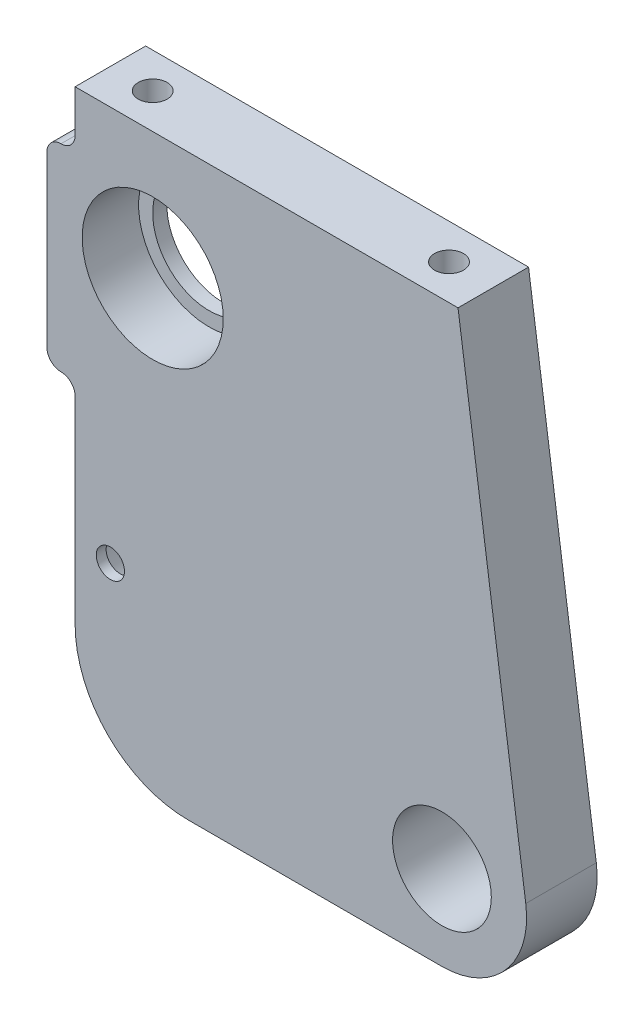
SolidWorks part; units mm, degrees
material "7075-T6, Plate (SS)"
ref_plane "前视基准面" through (0, 0, 0) normal (0, 0, 1) x (1, 0, 0)
ref_plane "上视基准面" through (0, 0, 0) normal (0, 1, 0) x (1, 0, 0)
ref_plane "右视基准面" through (0, 0, 0) normal (1, 0, 0) x (0, 0, -1)
sketch "草图1" plane through (0, 0, 0) normal (0, 0, 1) x (1, 0, 0)
  line L1 (0, 0) -> (34, 0)
  line L2 (0, 0) -> (0, -41)
  line L3 (0, -41) -> (34, -41)
  line L4 (34, 0) -> (34, -41)
  dimension "D1" = 34
  dimension "D3" = 41
extrude "拉伸1" add sketch "草图1" along normal blind 5
fillet "圆角1" radius 8 1 edges at (0, -41, 2.5)
sketch "草图2" plane through (0, 0, 5) normal (0, 0, 1) x (1, 0, 0)
  line L0 (0, 0) -> (0, -33) construction
  line L2 (8, -41) -> (34, -41) construction
  circle A0 centre (26, -35) radius 3.5
  dimension "D2" = 6
  dimension "D3" = 7
  dimension "D1" = 26
extrude "拉伸2" cut sketch "草图2" against normal up to surface (5 mm away) up to face at (14.8686, -23.3314, 0)
sketch "草图3" plane through (0, 0, 5) normal (0, 0, 1) x (1, 0, 0)
  line L0 (0, 0) -> (0, -33) construction
  line L1 (0, -41) -> (34, -41) construction
  circle A0 centre (5.5, -9) radius 4
  dimension "D1" = 5.5
  dimension "D2" = 32
  dimension "D3" = 8
extrude "拉伸3" cut sketch "草图3" against normal up to surface (5 mm away) up to face at (29.5, -35, 0)
sketch "草图4" plane through (0, 0, 5) normal (0, 0, 1) x (1, 0, 0)
  circle A0 centre (5.5, -9) radius 5
  dimension "D1" = 10
extrude "拉伸4" cut sketch "草图4" against normal blind 4
sketch "草图5" plane through (0, 0, 0) normal (0, 1, 0) x (1, 0, 0)
  line L0 (3, -2.5) -> (24, -2.5)
  line L1 (34, 0) -> (0, 0) construction
  line L2 (17, 0) -> (17, -2.5) construction
  line L3 (0, -5) -> (0, 0) construction
  dimension "D1" = 2.5
  dimension "D2" = 21
  dimension "D3" = 3
hole_wizard "M2.5 螺纹孔1" positions "3D草图1" profile "草图6" tap size "M2.5" standard "GB"
sketch3d "3D草图1"
  point P0 (3, 0, 2.5)
  point P3 (24, 0, 2.5)
sketch "草图6" plane through (3, 0, 2.5) normal (1, 0, 0) x (0, 0, 1)
  line L0 (0, 0) -> (0, 7.9659)
  line L1 (0, 7.9659) -> (1.025, 7.35)
  line L2 (1.025, 7.35) -> (1.025, 0)
  line L5 (1.025, 0) -> (0, 0)
  line L10 (0, 7.9659) -> (-1.025, 7.35) construction
  line L11 (0, -6.35) -> (0, 107.95) construction
  dimension "螺纹孔钻头直径" = 2.05
  dimension "螺纹孔钻头深度" = 7.35
  dimension "导头角度" = 118
cosmetic thread "孔螺蚊线1" parameters "D1"=6, "D2"=2.5
cosmetic thread "孔螺蚊线2" parameters "D1"=6, "D2"=2.5
chamfer "倒角1" [suppressed] distance 0.5 angle 45
chamfer "倒角2" [suppressed] distance 0.5 angle 45
sketch "草图7" plane through (0, 0, 0) normal (0, 0, -1) x (-1, 0, 0)
  line L1 (-8, -41) -> (-34, -41) construction
  line L2 (-31.9416, -34.165) -> (-27.14, 0)
  line L3 (-34, 0) -> (0, 0) construction
  line L4 (-26, -41) -> (-34, -41)
  line L5 (-34, -41) -> (-34, 0) construction
  line L6 (-34, -41) -> (-34, 0)
  line L7 (-34, 0) -> (-27.14, 0)
  arc A0 (-31.9416, -34.165) -> (-26, -41) centre (-26, -35) ccw
  circle A1 centre (-26, -35) radius 3.5 construction
  dimension "D1" = 6
  dimension "D2" = 8
extrude "拉伸5" cut sketch "草图7" against normal up to surface (5 mm away) up to face at (10.5, -9, 5)
sketch "Sketch1" plane through (0, 0, 0) normal (0, 0, -1) x (-1, 0, 0)
  line L0 (-26, -41) -> (-12, -41)
  line L1 (0, 0) -> (0, -33) construction
  line L2 (0, -28.0198) -> (0, -29)
  line L3 (-29.4415, -39.9149) -> (0, -28.0198)
  line L4 (-26, -35) -> (-29.4415, -39.9149) construction
  line L5 (-8, -41) -> (-26, -41) construction
  arc A0 (-31.9416, -34.165) -> (-26, -41) centre (-26, -35) ccw construction
  arc A1 (-29.4415, -39.9149) -> (-26, -41) centre (-26, -35) ccw
  arc A3 (0, -29) -> (-12, -41) centre (-12, -29) cw
  dimension "D1" = 12
  dimension "D2" = 55
  dimension "D3" = 22
  dimension "D4" = 0
sketch "草图8" plane through (0, 0, 0) normal (0, 0, -1) x (-1, 0, 0)
  line L0 (-8, -41) -> (-26, -41) construction
  line L1 (0, 0) -> (0, -33) construction
  circle A0 centre (-2.5, -28) radius 1
  dimension "D3" = 2
  dimension "D1" = 13
  dimension "D2" = 2.5
extrude "拉伸6" cut sketch "草图8" against normal up to surface (5 mm away) up to face at (15.497, -25.3626, 5)
sketch "草图9" plane through (0, 0, 0) normal (0, 0, -1) x (-1, 0, 0)
  line L3 (-7.1, -31.0997) -> (-0.5, -31.0997)
  line L4 (-2.5, -28) -> (-4, -28) construction
  line L5 (-2.5, -28) -> (-2.5, -23.308) construction
  line L6 (-4, -20.9273) -> (-4, -22.5) construction
  line L7 (-7.1, -31.0997) -> (-7.5, -31.0997)
  line L17 (-7.5, -31.0997) -> (-7.5, -30.7)
  line L18 (-7.5, -30.7) -> (-7.5, -23.5)
  line L19 (-7.5, -23.5) -> (-7.5, -22.1)
  line L20 (-7.5, -22.1) -> (-6.1, -22.1)
  line L21 (-1.9, -22.1) -> (-6.1, -22.1)
  line L22 (-1.9, -22.1) -> (-0.5, -22.1)
  line L23 (-0.5, -22.1) -> (-0.5, -23.5)
  line L24 (-0.5, -30.7) -> (-0.5, -23.5)
  line L25 (-0.5, -30.7) -> (-0.5, -31.0997)
  line L32 (-7.1, -28) -> (-7.596, -28) construction
  line L42 (-4, -28) -> (-4, -31.0273) construction
  point P10 (-4, -28)
  point P19 (-0.9, -22.5)
  point P22 (-7.1, -22.5)
  point P25 (-7.1, -31.7)
  dimension "D1" = 1.5
  dimension "D3" = 9.2
  dimension "D4" = 6.2
extrude "拉伸7" cut sketch "草图9" against normal blind 2.5
sketch "草图10" plane through (0, 0, 2.5) normal (0, 0, -1) x (-1, 0, 0)
  circle A0 centre (-4, -28) radius 3
  dimension "D1" = 6
extrude "拉伸8" cut sketch "草图10" against normal blind 1.8
sketch "草图11" plane through (0, 0, 5) normal (0, 0, -1) x (-1, 0, 0)
  line L0 (-4, -28) -> (-4, -35) construction
  line L1 (-4, -28) -> (-9.5, -28) construction
  line L2 (-4, -30) -> (-9.5, -30)
  dimension "D1" = 7
  dimension "D2" = 5.5
  dimension "D3" = 5.5
  dimension "D4" = 2
hole_wizard "M2.5 Tapped Hole2" [suppressed] positions "3D草图2" profile "草图12" tap size "M2.5" standard "GB"
sketch3d "3D草图2"
  point P0 (9.5, -25.5, 5)
  point P3 (4, -31.5, 5)
sketch "草图12" plane through (9.5, -25.5, 5) normal (1, 0, 0) x (0, -1, 0)
  line L0 (0, 0) -> (0, 6.9659)
  line L1 (0, 6.9659) -> (1.025, 6.35)
  line L2 (1.025, 6.35) -> (1.025, 0)
  line L5 (1.025, 0) -> (0, 0)
  line L10 (0, 6.9659) -> (-1.025, 6.35) construction
  line L11 (0, -6.35) -> (0, 107.95) construction
  dimension "Tap Drill Dia." = 2.05
  dimension "Tap Drill Depth" = 6.35
  dimension "Drill Angle" = 118
cosmetic thread "Hole Thread5" [suppressed] parameters "D1"=5, "D2"=2.5
cosmetic thread "Hole Thread6" [suppressed] parameters "D1"=5, "D2"=2.5
chamfer "倒角3" [suppressed] distance 0.2 angle 45
sketch "草图15" plane through (0, 0, 0) normal (0, 0, -1) x (-1, 0, 0)
  line L1 (0, 0) -> (0, -33) construction
  line L2 (-27.14, 0) -> (0, 0) construction
  circle A0 centre (-16, -28.5) radius 4
  dimension "D1" = 8
  dimension "D3" = 16
  dimension "D2" = 28.5
sketch "草图20" plane through (0, 0, 0) normal (-1, 0, 0) x (0, 0, 1)
  line L0 (5, -17) -> (5, -5)
  line L1 (5, 0) -> (5, -33) construction
  line L2 (5, -5) -> (0, -5)
  line L3 (0, 0) -> (0, -33) construction
  line L4 (0, -5) -> (0, -17)
  line L5 (0, -17) -> (5, -17)
  line L7 (5, 0) -> (0, 0) construction
  dimension "D1" = 5
  dimension "D2" = 12
extrude "凸台-拉伸1" add sketch "草图20" along normal blind 3
fillet "圆角2" radius 1 4 edges at (0, -5, 2.5) (0, -17, 2.5) (-3, -17, 2.5) (-3, -5, 2.5)
sketch "草图21" plane through (0, 0, 0) normal (0, 0, -1) x (-1, 0, 0)
  line L0 (0, 0) -> (0, -41) construction
  line L1 (0, 0) -> (-34, 0) construction
  point P0 (-7, -3)
  dimension "D1" = 7
  dimension "D2" = 3
sketch "草图25" plane through (0, 0, 5) normal (0, 0, 1) x (1, 0, 0)
  line L0 (0, 0) -> (0, -20.4816)
  line L1 (0, -20.4816) -> (-11.5435, -18.6029)
  line L2 (-11.5435, -18.6029) -> (-5.1339, -2.1001)
  line L3 (-5.1339, -2.1001) -> (0, 0)
extrude "切除-拉伸1" cut sketch "草图25" against normal blind 10
sketch "草图26" plane through (0, 0, 5) normal (0, 0, 1) x (1, 0, 0)
  line L1 (0, 0) -> (0, -33) construction
  line L2 (0, -4) -> (-2, -4)
  line L3 (-2, -4) -> (-2, -18)
  line L4 (-2, -18) -> (0, -18)
  line L5 (0, -18) -> (0, -4)
extrude "凸台-拉伸2" add sketch "草图26" against normal blind 5
fillet "圆角3" radius 1 1 edges at (0, -4, 2.5) type face fillet first side face at (0, -2, 2.5) second side face at (-1, -4, 2.5)
fillet "圆角4" radius 1 1 edges at (0, -18, 2.5) type face fillet first side face at (-1, -18, 2.5) second side face at (0, -25.5, 2.5)
fillet "圆角5" radius 1 3 edges at (-2, -4, 2.5) (-1.5, -4, 5) (-1.5, -4, 0)
fillet "圆角6" radius 1 3 edges at (-1.5, -18, 0) (-2, -18, 2.5) (-1.5, -18, 5)
